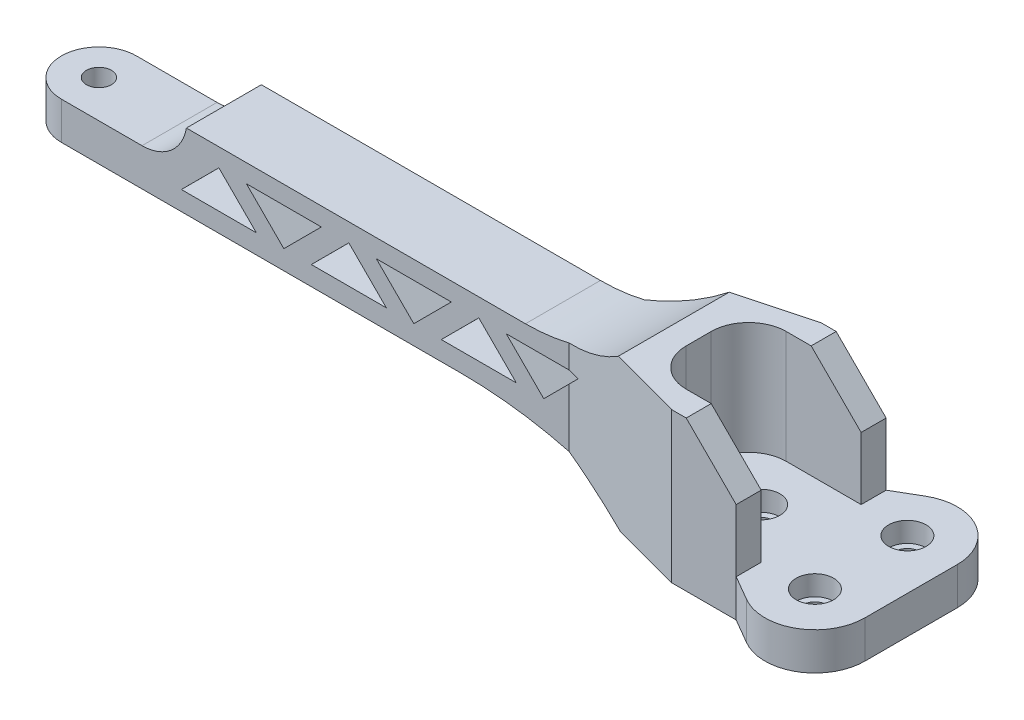
SolidWorks part; units mm, degrees
ref_plane "Front Plane" through (0, 0, 0) normal (0, 0, 1) x (1, 0, 0)
ref_plane "Top Plane" through (0, 0, 0) normal (0, 1, 0) x (1, 0, 0)
ref_plane "Right Plane" through (0, 0, 0) normal (1, 0, 0) x (0, 0, -1)
sketch "Sketch1" plane through (0, 0, 0) normal (0, 0, 1) x (1, 0, 0)
  line L0 (0, 0) -> (-91.5455, 0)
  line L1 (-91.5455, 0) -> (-91.5455, 15)
  line L2 (-91.5455, 15) -> (-44.2938, 15)
  line L6 (208.4545, 24.502) -> (208.4545, 0)
  line L9 (208.4545, -15.498) -> (154.5538, -15.498)
  line L12 (-26.5455, 30) -> (109.1263, 30)
  line L13 (153.4545, 44.502) -> (188.4545, 44.502)
  line L14 (188.4545, 44.502) -> (208.4545, 24.502)
  line L15 (0, 0) -> (83.3978, 0)
  line L16 (208.4545, 0) -> (208.4545, -15.498)
  arc A0 (-44.2938, 15) -> (-26.5455, 30) centre (-44.2938, 33) ccw
  arc A1 (109.1263, 30) -> (153.4545, 44.502) centre (109.1263, 105) ccw
  arc A2 (83.3978, 0) -> (154.5538, -15.498) centre (83.3978, -171.0979) cw
  point P10 (208.4545, 44.502)
  dimension "D1" = 18
  dimension "D2" = 75
  dimension "D13" = 171.0979
  dimension "D3" = 15
  dimension "D4" = 65
  dimension "D6" = 245
  dimension "D7" = 300
  dimension "D8" = 30
  dimension "D10" = 20
  dimension "D11" = 45
  dimension "D12" = 60
  dimension "D14" = 91.5455
  dimension "D15" = 83.3978
extrude "Boss-Extrude1" add sketch "Sketch1" along normal blind 15 and the other way blind 15
fillet "Fillet1" radius 15 2 edges at (-91.5455, 7.5, 15) (-91.5455, 7.5, -15)
sketch "Sketch2" plane through (0, -15.498, 0) normal (0, -1, 0) x (1, 0, 0)
  line L1 (109.1263, 15) -> (-26.5455, 15) construction
  line L11 (188.4545, -15) -> (188.4545, 15) construction
  line L13 (126.6188, 0) -> (153.4545, 0) construction
  line L16 (126.6188, -15) -> (153.4545, -22.1906)
  line L17 (208.4545, -15) -> (208.4545, 15) construction
  line L18 (153.4545, -15) -> (153.4545, 15) construction
  line L19 (153.4545, -22.1906) -> (182.5995, -30)
  line L20 (182.5995, -30) -> (208.4545, -30)
  line L26 (208.4545, 30) -> (182.5995, 30)
  line L27 (182.5995, 30) -> (153.4545, 22.1906)
  line L28 (153.4545, 22.1906) -> (126.6188, 15)
  line L29 (154.5538, 15) -> (83.3978, 15) construction
  line L31 (109.1263, -15) -> (-26.5455, -15) construction
  line L33 (248.4545, -18.5) -> (248.4545, 18.5)
  line L34 (208.4545, -30) -> (208.4545, 30)
  line L35 (188.4545, -41.8202) -> (188.4545, 44.1398) construction
  line L36 (208.4545, 30) -> (218.3934, 35.7851)
  line L37 (208.4545, -30) -> (218.3934, -35.7851)
  line L38 (126.6188, 15) -> (126.6188, -15)
  line L39 (83.3978, -15) -> (154.5538, -15) construction
  arc A2 (218.3934, -35.7851) -> (248.4545, -18.5) centre (228.4545, -18.5) ccw
  arc A4 (248.4545, 18.5) -> (218.3934, 35.7851) centre (228.4545, 18.5) ccw
  point P0 (153.4545, 0)
  point P2 (0, 0)
  point P15 (131.2904, -16.4359)
  point P28 (248.4545, -18.5)
  point P29 (228.4545, -38.5)
  point P30 (248.4545, 18.5)
  point P31 (228.4545, 38.5)
  point P37 (125.9316, 0)
  point P38 (126.0288, 0)
  point P40 (0, 0)
  point P41 (0, 0)
  point P42 (125.9316, 15)
  point P43 (126.3297, 15.1067)
  point P44 (0, 0)
  point P45 (0, 0)
  point P46 (125.94, 15)
  point P47 (126.3896, 15.1227)
  point P48 (0, 0)
  point P49 (0, 0)
  point P50 (0, 0)
  point P51 (131.2904, -16.4359)
  point P52 (131.2904, -16.4359)
  point P53 (0, 0)
  point P54 (129.9404, -15)
  point P55 (153.4545, -22.3747)
  point P56 (117.6785, -12.7886)
  dimension "D5" = 77
  dimension "D8" = 38.5
  dimension "D3" = 274.1451
  dimension "D6" = 60
  dimension "D9" = 20
  dimension "D11" = 37
  dimension "D2" = 165
  dimension "D4" = 165
  dimension "D7" = 300
  dimension "D10" = 20
  dimension "D12" = 30
  dimension "D13" = 30
  dimension "D14" = 30
  dimension "D15" = 245
extrude "Boss-Extrude2" add sketch "Sketch2" against normal blind 60 contours L26 L27 L28 L38 L16 L19 L20 L34
extrude "Cut-Extrude5" cut sketch "Sketch1<6>" against normal blind 43 and the other way blind 43 flip side to cut
sketch "Sketch1<6>" plane through (0, 0, 0) normal (0, 0, 1) x (1, 0, 0) same geometry as "Sketch1"
sketch "Sketch3" plane through (0, -15.498, 0) normal (0, -1, 0) x (1, 0, 0)
  line L0 (208.4545, -30) -> (218.3934, -35.7851)
  line L1 (208.4545, 30) -> (218.3934, 35.7851)
  line L2 (248.4545, 18.5) -> (248.4545, -18.5)
  line L3 (208.4545, -30) -> (208.4545, 30)
  arc A0 (218.3934, -35.7851) -> (248.4545, -18.5) centre (228.4545, -18.5) ccw
  arc A1 (248.4545, 18.5) -> (218.3934, 35.7851) centre (228.4545, 18.5) ccw
extrude "Boss-Extrude3" add sketch "Sketch3" against normal blind 15
sketch "Sketch4" plane through (0, -0.498, 0) normal (0, 1, 0) x (1, 0, 0)
  line L0 (208.4545, 30) -> (208.4545, -30) construction
  line L1 (208.4545, 20) -> (178.4545, 20)
  line L2 (208.4545, 20) -> (208.4545, -20)
  line L3 (208.4545, -20) -> (178.4545, -20)
  line L4 (163.4545, 5) -> (163.4545, -5)
  line L7 (126.6188, 0) -> (153.4545, 0) construction
  arc A0 (178.4545, -20) -> (163.4545, -5) centre (178.4545, -5) cw
  arc A1 (178.4545, 20) -> (163.4545, 5) centre (178.4545, 5) ccw
  dimension "D4" = 15
  dimension "D1" = 40
  dimension "D2" = 20
  dimension "D3" = 45
extrude "Cut-Extrude7" cut sketch "Sketch4" along normal through all
sketch "Sketch7" plane through (0, -0.498, 0) normal (0, 1, 0) x (1, 0, 0)
sketch "Sketch9" plane through (0, -0.498, 0) normal (0, 1, 0) x (1, 0, 0)
  line L0 (-101.1739, 0) -> (292.1993, 0) construction
  line L2 (188.4545, 39.3609) -> (188.4545, -59.7998) construction
sketch "Sketch10" plane through (0, -0.498, 0) normal (0, 1, 0) x (1, 0, 0)
  line L0 (-101.1739, 0) -> (292.1993, 0) construction
  line L1 (188.4545, 39.3609) -> (188.4545, -59.7998) construction
  point P0 (188.4545, 0)
  point P6 (228.4545, 18.5)
  point P9 (228.4545, -18.5)
hole_wizard "CBORE for M5 Hex Head Bolt1" positions "Sketch10" profile "Sketch8" counterbore size "M5" standard "ISO"
sketch "Sketch8" plane through (188.4545, -0.498, 0) normal (1, 0, 0) x (0, 0, 1)
  line L0 (0, 0) -> (0, 23.0043)
  line L1 (0, 23.0043) -> (5, 20)
  line L2 (5, 20) -> (5, 8)
  line L3 (5, 8) -> (7.5, 8)
  line L4 (7.5, 8) -> (7.5, 0)
  line L5 (7.5, 0) -> (0, 0)
  line L10 (0, 23.0043) -> (-5, 20) construction
  line L11 (0, -6.35) -> (0, 107.95) construction
  dimension "Hole Dia." = 10
  dimension "Hole Depth" = 20
  dimension "C'Bore Dia." = 15
  dimension "C'Bore Depth" = 8
  dimension "Drill Angle" = 118
sketch "Sketch11" plane through (0, 15, 0) normal (0, 1, 0) x (1, 0, 0)
  point P5 (-76.5455, 0)
hole_wizard "Ø10.0mm Dowel Hole1" positions "Sketch11" profile "Sketch13" hole size "Ø10.0" standard "ISO" end condition through all
sketch "Sketch13" plane through (-76.5455, 15, 0) normal (1, 0, 0) x (0, 0, 1)
  line L0 (0, 0) -> (0, 30.498)
  line L1 (0, 30.498) -> (5, 30.498)
  line L2 (5, 30.498) -> (5, 0)
  line L5 (5, 0) -> (0, 0)
  line L11 (0, -6.35) -> (0, 107.95) construction
  dimension "Thru Hole Dia." = 10
  dimension "Thru Hole Depth" = 30.498
sketch "Sketch14" plane through (0, 0, 15) normal (0, 0, 1) x (1, 0, 0)
  line L0 (-28.5455, 7.6871) -> (-13.5455, 22.7049)
  line L1 (-13.5455, 22.7049) -> (1.4545, 7.6871)
  line L2 (1.4545, 7.6871) -> (-28.5455, 7.6871)
  line L3 (-91.5455, 15) -> (-91.5455, 0) construction
  line L4 (-13.5455, 22.7049) -> (-47.0468, 56.2062) construction
  line L5 (-28.5455, 7.6871) -> (-98.2468, 7.6871) construction
  line L6 (-28.5455, 7.6871) -> (-28.5455, -37.5174) construction
  line L7 (-13.5455, 22.7049) -> (-50.4735, -14.223) construction
  line L8 (12.4545, 7.6871) -> (-2.5455, 22.7049)
  line L9 (27.4545, 22.7049) -> (12.4545, 7.6871)
  line L10 (-2.5455, 22.7049) -> (27.4545, 22.7049)
  line L11 (12.4545, 49.2931) -> (12.4545, -45.6137) construction
  line L12 (49.4545, 22.7049) -> (79.4545, 22.7049)
  line L13 (23.4545, 7.6871) -> (38.4545, 22.7049)
  line L14 (53.4545, 7.6871) -> (23.4545, 7.6871)
  line L15 (38.4545, 22.7049) -> (53.4545, 7.6871)
  line L16 (64.4545, 7.6871) -> (49.4545, 22.7049)
  line L17 (79.4545, 22.7049) -> (64.4545, 7.6871)
  line L19 (75.4545, 7.6871) -> (90.4545, 22.7049)
  line L20 (105.4545, 7.6871) -> (75.4545, 7.6871)
  line L21 (90.4545, 22.7049) -> (105.4545, 7.6871)
  line L22 (116.4545, 7.6871) -> (101.4545, 22.7049)
  line L23 (131.4545, 22.7049) -> (116.4545, 7.6871)
  line L24 (-2.5455, 22.7049) -> (49.4545, 22.7049) construction
  line L25 (101.4545, 22.7049) -> (131.4545, 22.7049) [skipped]
  line L26 (101.4545, 22.7049) -> (131.4545, 22.7049)
  dimension "D1" = 63
  dimension "D2" = 45
  dimension "D3" = 30
  dimension "D4" = 21.2258
  dimension "D5" = 15
  dimension "D6" = 45
  dimension "D7" = 11
  dimension "D8" = 3
  dimension "D9" = 52
extrude "Cut-Extrude9" cut sketch "Sketch14" against normal through all
sketch "Sketch16" plane through (4.7318, 0, -17.6595) normal (-0.2588, 0, 0.9659) x (0.9659, 0, 0.2588)
sketch "Sketch18" plane through (4.7318, 0, -17.6595) normal (-0.2588, 0, 0.9659) x (0.9659, 0, 0.2588)
  line L0 (126.1866, 22.7049) -> (131.19, 22.7049)
  line L1 (131.19, 22.7049) -> (126.1866, 17.8635)
  line L2 (126.1866, 17.8635) -> (126.1866, 22.7049)
extrude "Cut-Extrude14" cut sketch "Sketch14<3>" along direction (0, 0, -1) on the side of the normal through all contours L26 L23 L22
sketch "Sketch14<3>" plane through (0, 0, 15) normal (0, 0, 1) x (1, 0, 0) same geometry as "Sketch14"
